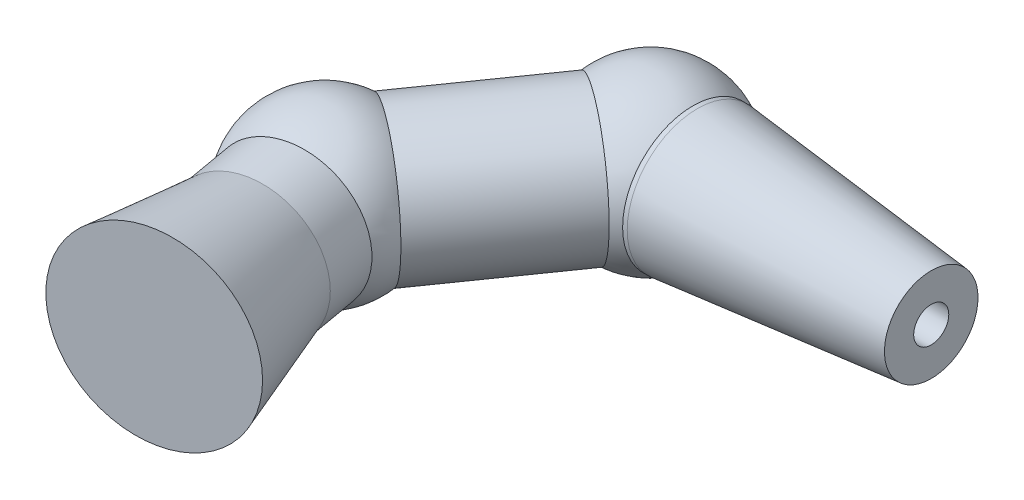
SolidWorks part; units mm, degrees
ref_plane "Plan de face" through (0, 0, 0) normal (0, 0, 1) x (1, 0, 0)
ref_plane "Plan de dessus" through (0, 0, 0) normal (0, 1, 0) x (1, 0, 0)
ref_plane "Plan de droite" through (0, 0, 0) normal (1, 0, 0) x (0, 0, -1)
sketch "Esquisse1" plane through (0, 0, 0) normal (1, 0, 0) x (0, 0, -1)
  circle A0 centre (0, 0) radius 3
  circle A1 centre (0, 0) radius 0.75
  dimension "D1" = 1.5
  dimension "D2" = 6
extrude "Boss.-Extru.1" add sketch "Esquisse1" along normal blind 12
chamfer "Chanfrein1" distance 10 distance2 1 1 edges at (12, 0, -3) first distance on face at (12, 0, -3)
sketch "Esquisse3" plane through (0, 0, 0) normal (-1, 0, 0) x (0, 0, 1)
  line L0 (0, -4.34) -> (0, 10.2923) construction
ref_plane "Plan1" through (0, 0, 0) normal (-0.5736, 0, 0.8192) x (0, 1, 0)
sketch "Esquisse2" plane through (0, 0, 0) normal (-1, 0, 0) x (0, 0, 1)
  line L0 (0, 3.5) -> (0, -3.5)
  arc A0 (0, 3.5) -> (0, -3.5) centre (0, 0) ccw
  dimension "D1" = 3.5
revolve "Révolution1" add sketch "Esquisse2" angle 360 about L0
sketch "Esquisse4" plane through (0, 0, 0) normal (-0.5736, 0, 0.8192) x (0, 1, 0)
  circle A0 centre (0, 0) radius 3
  dimension "D1" = 6
extrude "Boss.-Extru.2" add sketch "Esquisse4" along normal blind 10
sketch "Esquisse5" plane through (-5.7358, 0, 8.1915) normal (-0.5736, 0, 0.8192) x (0.8192, 0, 0.5736)
  line L0 (0, -5.8836) -> (0, 9.6722) construction
ref_plane "Plan2" through (1.2279, 0, 6.9636) normal (0.1736, 0, 0.9848) x (0, 1, 0)
sketch "Esquisse7" plane through (-5.7358, 0, 8.1915) normal (-0.5736, 0, 0.8192) x (0.8192, 0, 0.5736)
  line L0 (0, 3.5) -> (0, -3.5)
  arc A0 (0, 3.5) -> (0, -3.5) centre (0, 0) ccw
revolve "Révolution2" add sketch "Esquisse7" angle 360 about L0
sketch "Esquisse8" plane through (1.2279, 0, 6.9636) normal (0.1736, 0, 0.9848) x (0, 1, 0)
  line L0 (-5.8836, 7.0711) -> (9.6722, 7.0711) construction
  circle A0 centre (0, 7.0711) radius 3
  circle A1 centre (0, 7.0711) radius 3.5 construction
  dimension "D1" = 6
extrude "Boss.-Extru.3" add sketch "Esquisse8" along normal blind 4
sketch "Esquisse10" plane through (1.9225, 0, 10.9029) normal (0.1736, 0, 0.9848) x (0.9848, 0, -0.1736)
  circle A0 centre (-7.0711, 0) radius 4
  dimension "D1" = 8
extrude "Boss.-Extru.4" add sketch "Esquisse10" along normal blind 5
chamfer "Chanfrein2" distance 1 distance2 5 1 edges at (-1.1019, 0, 11.4362) first distance on face at (-2.0867, 0, 11.6098)
